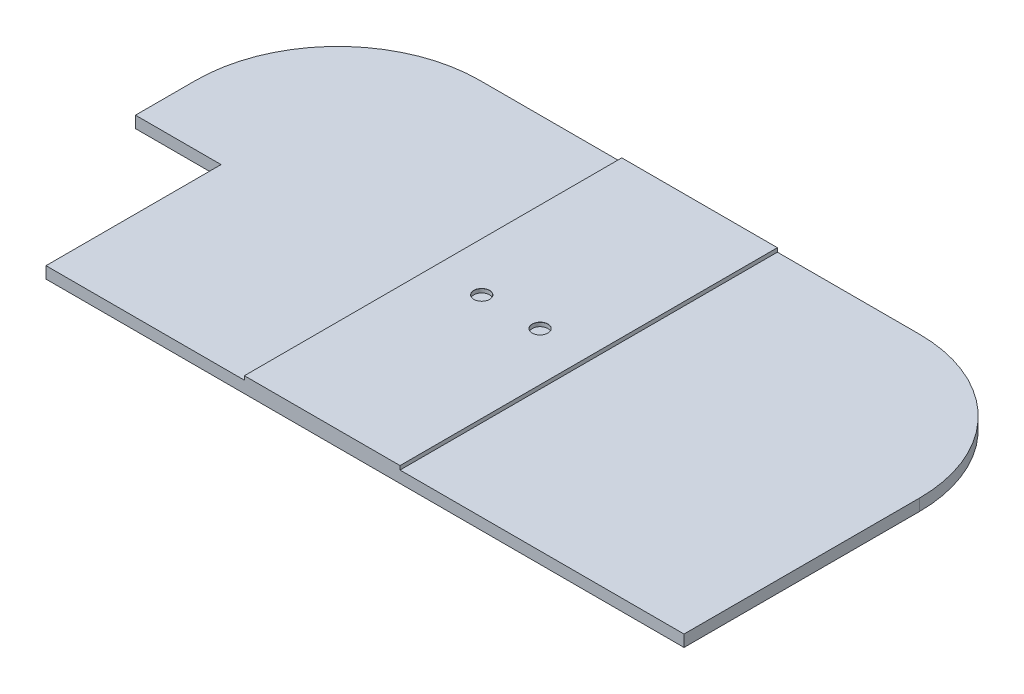
SolidWorks part; units mm, degrees
ref_plane "前基準面" through (0, 0, 0) normal (0, 0, 1) x (1, 0, 0)
ref_plane "上基準面" through (0, 0, 0) normal (0, 1, 0) x (1, 0, 0)
ref_plane "右基準面" through (0, 0, 0) normal (1, 0, 0) x (0, 0, -1)
sketch "草圖1" plane through (0, 0, 0) normal (0, 1, 0) x (1, 0, 0)
  line L1 (20, -48.5) -> (-20, -48.5)
  line L2 (20, -48.5) -> (20, 48.5)
  line L3 (20, 48.5) -> (-20, 48.5)
  line L4 (-20, -48.5) -> (-20, 48.5)
  line L5 (20, -48.5) -> (-20, 48.5) construction
  line L6 (20, 48.5) -> (-20, -48.5) construction
  point P0 (0, 0)
  dimension "D1" = 40
  dimension "D2" = 97
extrude "填料-伸長1" add sketch "草圖1" along normal blind 1
hole_wizard "Ø4.0mm 定位孔1" positions "草圖3" profile "草圖5" hole size "Ø4.0" standard "ISO" end condition through all
sketch "草圖3" plane through (0, 1, 0) normal (0, 1, 0) x (1, 0, 0)
  line L0 (-20, 0) -> (20, 0) construction
  line L1 (-20, 48.5) -> (-20, -48.5) construction
  line L2 (20, -48.5) -> (20, 48.5) construction
  line L5 (0, 48.5) -> (0, -48.5) construction
  line L6 (20, 48.5) -> (-20, 48.5) construction
  line L7 (-20, -48.5) -> (20, -48.5) construction
  point P0 (7.5, 0)
  point P24 (-7.5, 0)
  dimension "D1" = 15
sketch "草圖5" plane through (7.5, 1, 0) normal (1, 0, 0) x (0, 0, 1)
  line L0 (0, 0) -> (0, 1)
  line L1 (0, 1) -> (2, 1)
  line L2 (2, 1) -> (2, 0.025)
  line L3 (2, 0.025) -> (2.025, 0)
  line L5 (2.025, 0) -> (0, 0)
  line L6 (-2, 0.025) -> (-2.025, 0) construction
  line L11 (0, -6.35) -> (0, 107.95) construction
  dimension "貫穿孔直徑" = 4
  dimension "貫穿孔深度" = 1
  dimension "近端錐孔直徑" = 4.05
  dimension "近端錐孔角度" = 90
sketch "草圖6" plane through (0, 1, 0) normal (0, 1, 0) x (1, 0, 0)
  line L9 (20, 48.5) -> (-20, 48.5) construction
  line L10 (93, -48.5) -> (-93, -48.5)
  line L11 (93, -48.5) -> (93, 48.5)
  line L12 (93, 48.5) -> (-93, 48.5)
  line L13 (-93, -48.5) -> (-93, 48.5)
  line L14 (93, -48.5) -> (-93, 48.5) construction
  line L15 (93, 48.5) -> (-93, -48.5) construction
  point P0 (0, 0)
  dimension "D1" = 186
extrude "填料-伸長2" [suppressed] add sketch "草圖6" along normal blind 2
extrude "填料-伸長3" add sketch "草圖6<2>" against normal blind 3 from surface starting at face at (7.5, 0, 2)
sketch "草圖6<2>" plane through (0, 1, 0) normal (0, 1, 0) x (1, 0, 0) same geometry as "草圖6"
sketch "草圖7" [suppressed] plane through (0, 12, 0) normal (0, 1, 0) x (1, 0, 0)
  line L0 (-93, -48.5) -> (93, -48.5) construction
  line L1 (-93, -48.5) -> (-71, -48.5)
  line L2 (-93, -48.5) -> (-93, -3.5)
  line L3 (-93, -3.5) -> (-71, -3.5)
  line L4 (-71, -48.5) -> (-71, -3.5)
  line L5 (-93, 48.5) -> (-93, -48.5) construction
  dimension "D1" = 45
  dimension "D2" = 22
extrude "除料-伸長1" [suppressed] cut sketch "草圖7" against normal through all
fillet "圓角1" [suppressed] radius 36.5
fillet "圓角2" radius 36.5 2 edges at (93, -1.5, -48.5) (-93, -1.5, -48.5)
sketch "草圖8" plane through (0, 0, 0) normal (0, 1, 0) x (1, 0, 0)
  line L1 (-93, -48.5) -> (-71, -48.5)
  line L2 (-93, -48.5) -> (-93, -3.5)
  line L3 (-93, -3.5) -> (-71, -3.5)
  line L4 (-71, -48.5) -> (-71, -3.5)
  dimension "D1" = 22
  dimension "D2" = 45
extrude "除料-伸長2" cut sketch "草圖8" against normal through all
